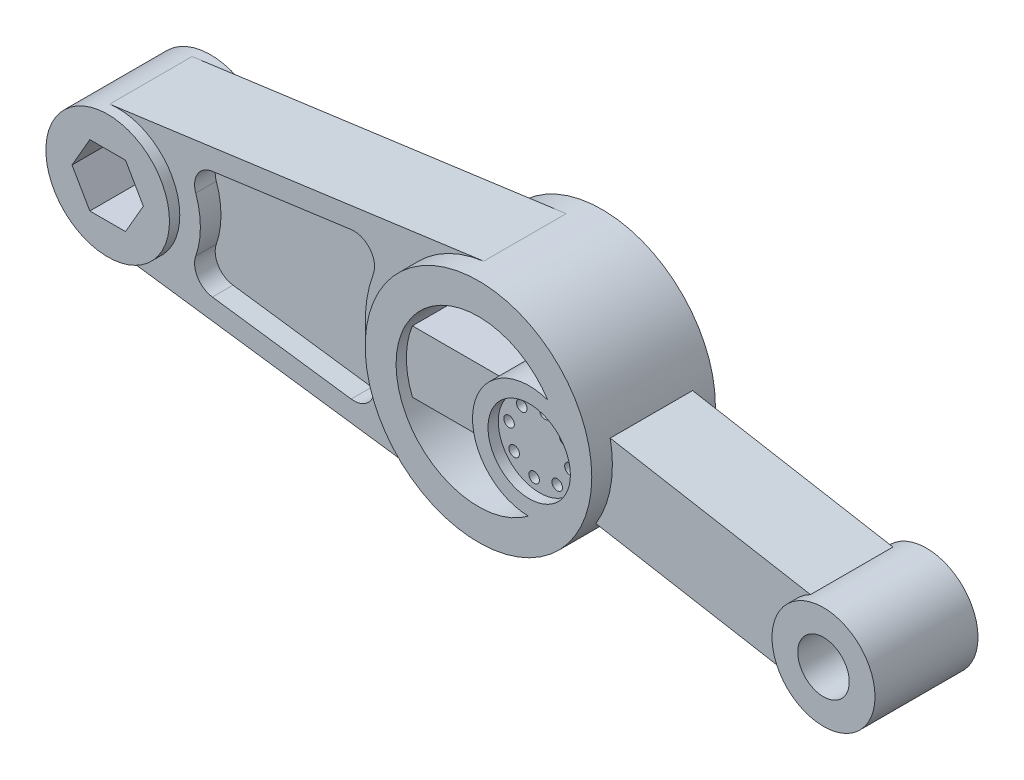
SolidWorks part; units mm, degrees
material "Copper"
ref_plane "Front Plane" through (0, 0, 0) normal (0, 0, 1) x (1, 0, 0)
ref_plane "Top Plane" through (0, 0, 0) normal (0, 1, 0) x (1, 0, 0)
ref_plane "Right Plane" through (0, 0, 0) normal (1, 0, 0) x (0, 0, -1)
ref_plane "CENTRE_Plane" through (185, 0, 0) normal (1, 0, 0) x (0, 0, -1)
ref_axis "CENTRE_Plane_Axis" through (185, 0, 33) along (0, 0, -1)
ref_plane "CENTRE_RIGHT_Plane" through (179.4216, -31.6369, 0) normal (0.9848, -0.1736, 0) x (0, 0, -1)
ref_plane "RIGHT_Plane" through (341.9148, -60.2888, 0) normal (0.9848, -0.1736, 0) x (0, 0, -1)
sketch "Sketch1" plane through (0, 0, 0) normal (0, 0, 1) x (1, 0, 0)
  line L0 (-4.0541, 29.7248) -> (177.5676, 54.4955)
  line L1 (-4.0541, -29.7248) -> (177.5676, -54.4955)
  arc A0 (-4.0541, 29.7248) -> (-4.0541, -29.7248) centre (0, 0) ccw
  arc A1 (177.5676, -54.4955) -> (177.5676, 54.4955) centre (185, 0) ccw
  dimension "D1" = 60
  dimension "D2" = 110
extrude "LEFT_ARM" add sketch "Sketch1" along normal mid plane 40
sketch "Sketch2" plane through (0, 0, 0) normal (0, 0, 1) x (1, 0, 0)
  circle A0 centre (0, 0) radius 30
  dimension "D1" = 60
extrude "LEFT_Boss" add sketch "Sketch2" along normal mid plane 50
sketch "Sketch4" plane through (0, 0, 25) normal (0, 0, 1) x (1, 0, 0)
  line L0 (33, 0) -> (-33, 0) construction
  line L1 (17.3205, 0) -> (8.6603, 15)
  line L2 (8.6603, 15) -> (-8.6603, 15)
  line L3 (-8.6603, 15) -> (-17.3205, 0)
  line L4 (-17.3205, 0) -> (-8.6603, -15)
  line L5 (-8.6603, -15) -> (8.6603, -15)
  line L6 (8.6603, -15) -> (17.3205, 0)
  circle A0 centre (0, 0) radius 15 construction
  dimension "D1" = 30
extrude "LEFT_Hex" cut sketch "Sketch4" against normal through all both and the other way through all
sketch "Sketch3" plane through (0, 0, 0) normal (0, 0, 1) x (1, 0, 0)
  circle A0 centre (185, 0) radius 55
  dimension "D1" = 110
extrude "CENTRE_Boss" add sketch "Sketch3" along normal mid plane 60
sketch "Sketch5" plane through (179.4216, -31.6369, 0) normal (0.9848, -0.1736, 0) x (0, 0, -1)
  line L0 (-33, 32.1249) -> (33, 32.1249) construction
  line L1 (-20, 12.1249) -> (20, 12.1249)
  line L2 (-20, 12.1249) -> (-20, 52.1249)
  line L3 (-20, 52.1249) -> (20, 52.1249)
  line L4 (20, 12.1249) -> (20, 52.1249)
  line L5 (-20, 12.1249) -> (20, 52.1249) construction
  line L6 (-20, 52.1249) -> (20, 12.1249) construction
  line L7 (0, 60.5) -> (0, -60.5) construction
  point P0 (0, 32.1249)
  dimension "D1" = 40
  dimension "D2" = 40
extrude "RIGHT_ARM" add sketch "Sketch5" along normal up to surface (165 mm away) up to plane "RIGHT_Plane"
sketch "RIGHT_ARM_CL" plane through (0, 0, 0) normal (0, 0, 1) x (1, 0, 0)
  line L0 (185, 0) -> (347.4933, -28.6519) construction
  line L1 (331.6454, -118.5296) -> (352.1843, -2.048) construction
sketch "Sketch7" plane through (0, 0, 0) normal (0, 0, 1) x (1, 0, 0)
  circle A0 centre (347.4933, -28.6519) radius 25
  dimension "D1" = 50
extrude "RIGHT_Boss" add sketch "Sketch7" along normal mid plane 50
sketch "Sketch8" plane through (0, 0, 25) normal (0, 0, 1) x (1, 0, 0)
  circle A0 centre (347.4933, -28.6519) radius 12.5
  dimension "D1" = 25
extrude "RIGHT_Boss_Hole" cut sketch "Sketch8" against normal through all
sketch "Sketch9" plane through (0, 0, 30) normal (0, 0, 1) x (1, 0, 0)
  circle A0 centre (185, 0) radius 40
  dimension "D1" = 80
extrude "CENTRE_Hole" cut sketch "Sketch9" against normal through all
sketch "Sketch10" plane through (0, 0, 0) normal (0, 0, 1) x (1, 0, 0)
  line L0 (185, 0) -> (347.4933, -28.6519) construction
  line L1 (168.9159, -91.2177) -> (189.9273, 27.944) construction
  circle A0 centre (209.6202, -4.3412) radius 27.5
  dimension "D1" = 55
  dimension "D2" = 25
extrude "CENTRE_Blob" add sketch "Sketch10" along normal mid plane 60
sketch "Sketch11" plane through (185, 0, 0) normal (1, 0, 0) x (0, 0, -1)
  line L1 (-25, -15) -> (25, -15)
  line L2 (-25, -15) -> (-25, 15)
  line L3 (-25, 15) -> (25, 15)
  line L4 (25, -15) -> (25, 15)
  line L5 (-25, -15) -> (25, 15) construction
  line L6 (-25, 15) -> (25, -15) construction
  point P0 (0, 0)
  dimension "D1" = 50
  dimension "D2" = 30
extrude "CENTRE_Beam" add sketch "Sketch11" along normal up to next and the other way up to next
sketch "Sketch12" plane through (0, 0, 30) normal (0, 0, 1) x (1, 0, 0)
  circle A0 centre (209.6202, -4.3412) radius 20
  dimension "D1" = 40
extrude "Cut-Extrude4" cut sketch "Sketch12" against normal blind 5
hole_wizard "1/4-20 Tapped Hole1" positions "Sketch13" profile "Sketch14" tap size "1/4-20" standard "ANSI Inch" end condition up to next
sketch "Sketch13" plane through (0, 0, 25) normal (0, 0, 1) x (1, 0, 0)
  line L0 (185, 0) -> (347.4933, -28.6519) construction
  circle A0 centre (209.6202, -4.3412) radius 20 construction
  point P0 (194.8481, -1.7365)
  dimension "D1" = 15
sketch "Sketch14" plane through (194.8481, -1.7365, 25) normal (1, 0, 0) x (0, -1, 0)
  line L0 (0, 0) -> (0, 55)
  line L1 (0, 55) -> (2.5527, 55)
  line L2 (2.5527, 55) -> (2.5527, 0)
  line L5 (2.5527, 0) -> (0, 0)
  line L11 (0, -6.35) -> (0, 107.95) construction
  dimension "Thru Tap Drill Dia." = 5.1054
  dimension "Thru Tap Drill Depth" = 55
cosmetic thread "Hole Thread1" parameters "D2"=6.35
pattern_circular "CirPattern1" count 8 over 360 about axis through (209.6202, -4.3412, 25) along (0, 0, 1) of "1/4-20 Tapped Hole1"
cosmetic thread "Hole Thread2" parameters "D2"=6.35
cosmetic thread "Hole Thread3" parameters "D2"=6.35
cosmetic thread "Hole Thread4" parameters "D2"=6.35
cosmetic thread "Hole Thread5" parameters "D2"=6.35
cosmetic thread "Hole Thread6" parameters "D2"=6.35
cosmetic thread "Hole Thread7" parameters "D2"=6.35
cosmetic thread "Hole Thread8" parameters "D2"=6.35
mirror "Mirror1" about plane through (0, 0, 0) normal (0, 0, 1) of "Cut-Extrude4"
sketch "Sketch15" plane through (0, 0, 20) normal (0, 0, 1) x (1, 0, 0)
  line L24 (132.445, 38.2488) -> (-2.7027, 19.8165)
  line L25 (-2.7027, -19.8165) -> (132.445, -38.2488)
  line L26 (132.445, 38.2488) -> (31.6206, 24.4978)
  line L27 (31.6206, -24.4978) -> (132.445, -38.2488)
  arc A12 (132.445, 38.2488) -> (132.445, -38.2488) centre (185, 0) ccw
  arc A13 (132.445, 38.2488) -> (132.445, -38.2488) centre (185, 0) ccw
  arc A23 (-5.4054, -39.6331) -> (-5.4054, 39.6331) centre (0, 0) ccw
  arc A24 (31.6206, -24.4978) -> (31.6206, 24.4978) centre (0, 0) ccw
  dimension "D1" = 10
  dimension "D2" = 10
extrude "Cut_OUT" cut sketch "Sketch15" against normal blind 10
fillet "Fillet1" radius 10 4 edges at (132.445, 38.2488, 15) (132.445, -38.2488, 15) (31.6206, -24.4978, 15) (31.6206, 24.4978, 15)
mirror "Mirror2" about plane through (0, 0, 0) normal (0, 0, 1) of "Fillet1", "Cut_OUT"
sketch "Sketch16" plane through (0, 0, 0) normal (0, 0, 1) x (1, 0, 0)
  line L0 (346.2777, -35.5456) -> (348.7088, -21.7583)
  line L1 (331.6454, -118.5296) -> (352.1843, -2.048) construction
  line L2 (348.7088, -21.7583) -> (320.3464, -16.7572)
  line L3 (320.3464, -16.7572) -> (317.9153, -30.5445)
  line L4 (317.9153, -30.5445) -> (346.2777, -35.5456)
  circle A0 centre (347.4933, -28.6519) radius 12.5 construction
  point P4 (347.4933, -28.6519)
  dimension "D1" = 14
  dimension "D2" = 28.8
extrude "KEYWAY" [suppressed] cut sketch "Sketch16" against normal through all both and the other way through all
mirror "Mirror3" [suppressed] about plane through (341.9148, -60.2888, 0) normal (0.9848, -0.1736, 0)
equation "\"D1@Sketch2\"=\"D1@Sketch1\""
equation "\"D1@Sketch3\"=\"D2@Sketch1\""
equation "\"D2@Sketch16\"=25+3.8"
